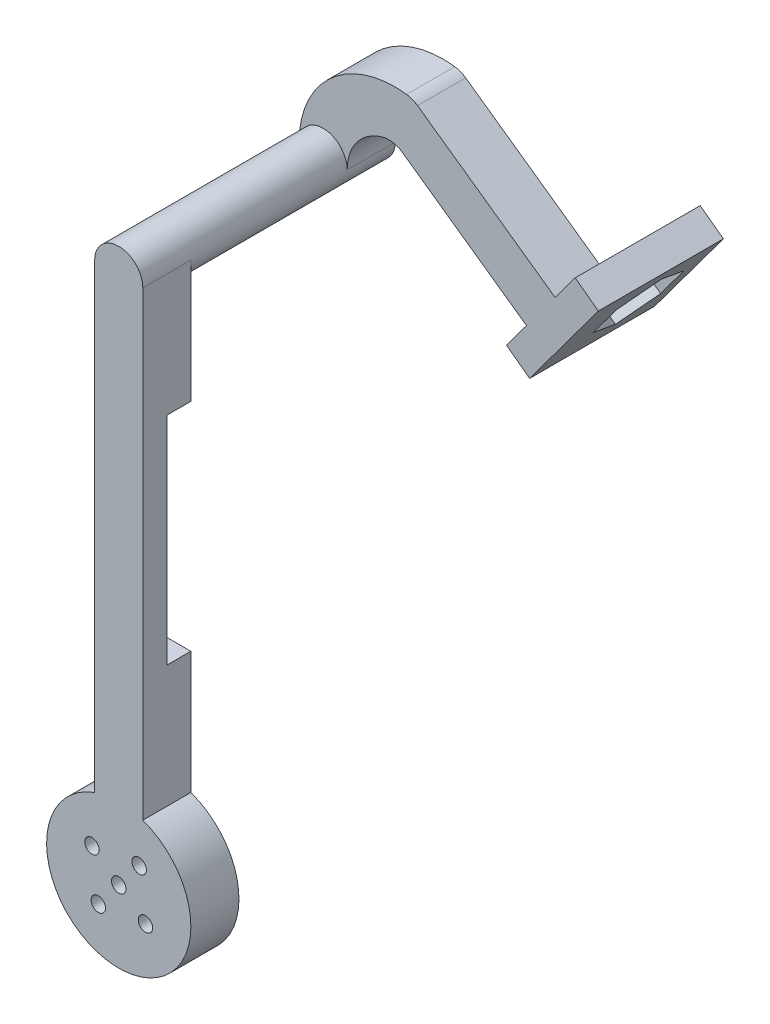
SolidWorks part; units mm, degrees
ref_plane "Front Plane" through (0, 0, 0) normal (0, 0, 1) x (1, 0, 0)
ref_plane "Top Plane" through (0, 0, 0) normal (0, 1, 0) x (1, 0, 0)
ref_plane "Right Plane" through (0, 0, 0) normal (1, 0, 0) x (0, 0, -1)
sketch "Sketch1" plane through (0, 0, 0) normal (0, 0, 1) x (1, 0, 0)
  line L0 (0, 0) -> (10, 0) construction
  line L1 (0, 0) -> (0, 70)
  line L2 (-10, 0) -> (-10, 70)
  line L4 (-10, 0) -> (0, 0)
  line L5 (-8.7897, 79.9265) -> (-8.7897, 79.9265)
  line L6 (-8.7897, 79.9265) -> (-8.7897, 79.9265)
  line L7 (-8.7897, 79.9265) -> (-8.7897, 79.9265)
  line L9 (-7.4908, 79.6801) -> (-7.4908, 79.6801)
  line L10 (-7.4908, 79.6801) -> (-7.4908, 79.6801)
  line L11 (-7.4908, 79.6801) -> (-7.4908, 79.6801)
  line L12 (11.5366, 78.8386) -> (37.5637, 60.4121)
  line L13 (-0.5952, 86.9223) -> (-0.5952, 86.9223)
  line L14 (-0.5952, 86.9223) -> (-0.5952, 86.9223)
  line L15 (-0.5952, 86.9223) -> (-0.5952, 86.9223)
  line L16 (14.637, 88.8961) -> (43.342, 68.5737)
  line L17 (10, 79.9265) -> (37.5637, 60.4121) construction
  line L18 (13.6868, 89.5688) -> (43.342, 68.5737) construction
  arc A2 (0, 70) -> (145.9412, 91.1284) centre (74.5, 70) cw construction
  arc A3 (-10, 70) -> (155.5306, 93.9645) centre (74.5, 70) cw construction
  arc A4 (0, 70) -> (7.3493, 79.5863) centre (9.9268, 70) cw
  arc A5 (-7.4908, 79.6801) -> (10.0738, 89.9262) centre (9.9268, 70) cw
  arc A6 (-10, 70) -> (-7.4908, 79.6801) centre (9.9268, 70) cw
  arc A8 (0, 70) -> (30, 101.2848) centre (31.3123, 70) cw construction
  arc A9 (-8.7897, 79.9265) -> (29.5809, 111.276) centre (31.3123, 70) cw construction
  arc A10 (-0.5952, 86.9223) -> (-0.5952, 86.9223) centre (-0.5952, 86.9223) cw
  arc A11 (-0.5952, 86.9223) -> (12.3579, 89.7779) centre (9.9268, 70) cw
  arc A12 (37.5637, 60.4121) -> (43.342, 68.5737) centre (40.4528, 64.4929) ccw
  arc A13 (0, 70) -> (10, 79.9265) centre (9.9268, 70) cw construction
  arc A14 (11.5366, 78.8386) -> (7.3493, 79.5863) centre (8.6475, 74.7578) ccw
  arc A15 (-0.5952, 86.9223) -> (13.6868, 89.5688) centre (9.9268, 70) cw construction
  arc A16 (14.637, 88.8961) -> (12.3579, 89.7779) centre (11.7479, 84.8152) ccw
  dimension "D7" = 5
  dimension "D8" = 5
  dimension "D1" = 10
  dimension "D2" = 70
  dimension "D3" = 10
  dimension "D5" = 10
  dimension "D4" = 10
  dimension "D6" = 10
extrude "Boss-Extrude1" add sketch "Sketch1" along normal blind 10
sketch "Sketch6" plane through (0, 0, 10) normal (0, 0, 1) x (1, 0, 0)
  line L0 (-5, 0) -> (-5, 140) construction
  line L1 (-10, 0) -> (0, 0) construction
  circle A0 centre (-5, 70) radius 5
  dimension "D1" = 140
extrude "Boss-Extrude4" add sketch "Sketch6" along normal blind 32.5
ref_plane "Plane2" through (0, 0, 26.25) normal (0, 0, 1) x (1, 0, 0)
sketch "Sketch10" plane through (0, 0, 0) normal (0, 0, -1) x (-1, 0, 0)
  line L0 (5, 0) -> (5, 45) construction
  line L1 (10, 0) -> (0, 0) construction
  line L3 (0, 45) -> (10, 45)
  line L4 (0, 45) -> (0, 0)
  line L5 (0, 0) -> (10, 0)
  line L6 (10, 45) -> (10, 0)
  line L7 (0, 45) -> (10, 0) construction
  line L8 (0, 0) -> (10, 45) construction
  point P4 (5, 22.5)
  dimension "D1" = 45
extrude "Cut-Extrude5" cut sketch "Sketch10" against normal blind 10
sketch "Sketch17" plane through (0, 0, 10) normal (0, 0, 1) x (1, 0, 0)
  line L3 (-10, 45) -> (0, 45)
  line L4 (0, 45) -> (0, 70)
  line L5 (-10, 70) -> (-10, 45)
  line L6 (-10, 45) -> (0, 45)
  line L7 (0, 45) -> (0, 70)
  line L8 (-10, 70) -> (-10, 45)
  arc A1 (-10, 70) -> (0, 70) centre (-5, 70) ccw
  arc A2 (-10, 70) -> (0, 70) centre (-5, 70) ccw
  dimension "D1" = 0
extrude "Cut-Extrude10" cut sketch "Sketch17" against normal blind 10
sketch "Sketch18" plane through (0, 0, 42.5) normal (0, 0, 1) x (1, 0, 0)
  line L0 (0, 70) -> (0, -25.8579)
  line L1 (-10, 70) -> (-10, -25.8579)
  line L2 (-10, -30) -> (0, -30) construction
  line L3 (-5, -30) -> (-5, -40) construction
  circle A0 centre (-5, 70) radius 5 construction
  arc A1 (0, 70) -> (-10, 70) centre (-5, 70) ccw
  arc A2 (-10, -25.8579) -> (0, -25.8579) centre (-5, -40) ccw
  dimension "D3" = 30
  dimension "D1" = 100
  dimension "D2" = 10
extrude "Boss-Extrude8" add sketch "Sketch18" along normal blind 10
sketch "Sketch19" plane through (0, 0, 42.5) normal (0, 0, -1) x (-1, 0, 0)
  circle A0 centre (5, -40) radius 1.5
  circle A1 centre (10.5657, -35.7546) radius 1.5
  circle A2 centre (0.7546, -34.4343) radius 1.5
  circle A3 centre (-0.5657, -44.2454) radius 1.5
  circle A4 centre (9.2454, -45.5657) radius 1.5
extrude "Cut-Extrude11" cut sketch "Sketch19" against normal through all
sketch "Sketch20" plane through (0, 0, 0) normal (0, 0, -1) x (-1, 0, 0)
  line L0 (-49.8182, 72.4883) -> (-34.3374, 51.5995) construction
  line L1 (-45.0835, 61.0611) -> (-40.4528, 64.4929) construction
  line L2 (-52.2285, 70.7021) -> (-47.408, 74.2746)
  line L3 (-37.9385, 51.4201) -> (-33.118, 54.9926)
  line L4 (-47.408, 74.2746) -> (-33.118, 54.9926)
  line L5 (-52.2285, 70.7021) -> (-37.9385, 51.4201)
  point P4 (-40.4528, 64.4929)
  point P14 (-49.8182, 72.4883)
  dimension "D1" = 26
  dimension "D2" = 6
  dimension "D3" = 24
extrude "Boss-Extrude9" add sketch "Sketch20" along normal blind 16
sketch "Sketch21" plane through (0, 0, 0) normal (0, 0, 1) x (1, 0, 0)
  line L18 (43.2377, 68.6475) -> (43.342, 68.5737) construction
  line L26 (43.2377, 68.6475) -> (43.342, 68.5737)
  line L36 (47.408, 74.2746) -> (43.2377, 68.6475)
  line L37 (43.2377, 68.6475) -> (43.342, 68.5737)
  line L38 (37.5637, 60.4121) -> (37.2822, 60.6114)
  line L39 (37.2822, 60.6114) -> (33.118, 54.9926)
  line L40 (33.118, 54.9926) -> (37.9385, 51.4201)
  line L41 (37.9385, 51.4201) -> (52.2285, 70.7021)
  line L42 (52.2285, 70.7021) -> (47.408, 74.2746)
  line L43 (47.408, 74.2746) -> (43.2377, 68.6475)
  line L44 (43.2377, 68.6475) -> (43.342, 68.5737)
  line L45 (37.5637, 60.4121) -> (37.2822, 60.6114)
  line L46 (37.2822, 60.6114) -> (33.118, 54.9926)
  line L47 (33.118, 54.9926) -> (37.9385, 51.4201)
  line L48 (37.9385, 51.4201) -> (52.2285, 70.7021)
  line L49 (52.2285, 70.7021) -> (47.408, 74.2746)
  arc A9 (37.5637, 60.4121) -> (43.342, 68.5737) centre (40.4528, 64.4929) ccw
  arc A10 (37.5637, 60.4121) -> (43.342, 68.5737) centre (40.4528, 64.4929) ccw
  dimension "D1" = 0
extrude "Boss-Extrude10" add sketch "Sketch21" along normal blind 10
sketch "Sketch22" plane through (-0.1091, 0.0809, 0) normal (0.8034, -0.5954, 0) x (0, 0, -1)
  line L1 (12.5, 71.8595) -> (12.5, 79.9424)
  line L2 (12.5, 79.9424) -> (5.5, 83.9839)
  line L3 (5.5, 83.9839) -> (-1.5, 79.9424)
  line L4 (-1.5, 79.9424) -> (-1.5, 71.8595)
  line L5 (-1.5, 71.8595) -> (5.5, 67.8181)
  line L6 (5.5, 67.8181) -> (12.5, 71.8595)
  circle A0 centre (5.5, 75.901) radius 7 construction
extrude "Cut-Extrude12" cut sketch "Sketch22" against normal up to surface (6 mm away) up to face at (40.2615, 64.6315, 1)
sketch "Sketch24" plane through (-10, 0, 0) normal (-1, 0, 0) x (0, 0, 1)
  line L0 (42.5, 22.0711) -> (52.5, 22.0711) construction
  line L1 (42.5, 70) -> (42.5, -25.8579) construction
  line L2 (52.5, 70) -> (52.5, -25.8579) construction
  line L3 (47.5, 44.5711) -> (47.5, -0.4289)
  line L4 (47.5, 44.5711) -> (42.5, 44.5711)
  line L5 (42.5, 44.5711) -> (42.5, -0.4289)
  line L6 (42.5, -0.4289) -> (47.5, -0.4289)
  point P9 (47.5, 22.0711)
  dimension "D1" = 45
extrude "Cut-Extrude14" cut sketch "Sketch24" against normal blind 10
